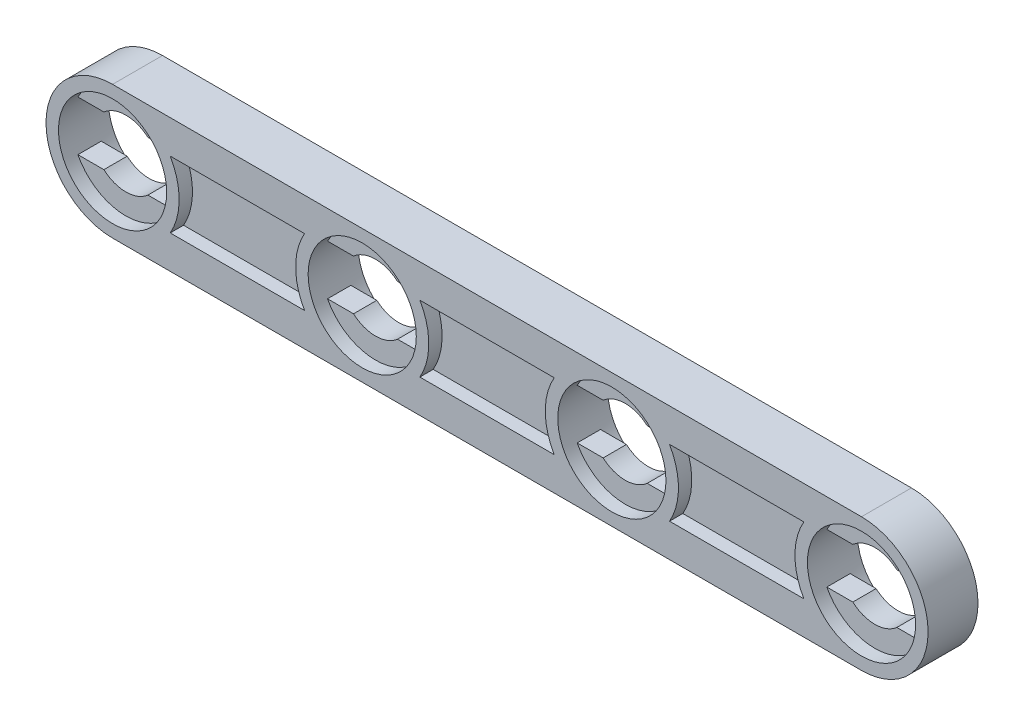
SolidWorks part; units mm, degrees
ref_plane "前视基准面" through (0, 0, 0) normal (0, 0, 1) x (1, 0, 0)
ref_plane "上视基准面" through (0, 0, 0) normal (0, 1, 0) x (1, 0, 0)
ref_plane "右视基准面" through (0, 0, 0) normal (1, 0, 0) x (0, 0, -1)
sketch "草图1" plane through (0, 0, 0) normal (0, 0, 1) x (1, 0, 0)
  line L1 (0, 4) -> (45, 4)
  line L3 (0, -4) -> (45, -4)
  arc A0 (0, 4) -> (0, -4) centre (0, 0) ccw
  arc A1 (45, -4) -> (45, 4) centre (45, 0) ccw
extrude "凸台-拉伸1" add sketch "草图1" against normal blind 3
sketch "草图2" plane through (0, 0, 0) normal (0, 0, 1) x (1, 0, 0)
  line L0 (1.3229, -1.5) -> (2.8831, -1.5)
  line L1 (-2.8831, -1.5) -> (-1.3229, -1.5)
  line L2 (1.3229, 1.5) -> (2.8831, 1.5)
  line L3 (-2.8831, 1.5) -> (-1.3229, 1.5)
  arc A0 (1.3229, 1.5) -> (-1.3229, 1.5) centre (0, 0) ccw
  arc A1 (-2.8831, 1.5) -> (-2.8831, -1.5) centre (0, 0) ccw
  arc A3 (2.8831, -1.5) -> (2.8831, 1.5) centre (0, 0) ccw
  arc A4 (-1.3229, -1.5) -> (1.3229, -1.5) centre (0, 0) ccw
extrude "切除-拉伸1" cut sketch "草图2" against normal up to next
sketch "草图3" plane through (0, 0, 0) normal (0, 0, 1) x (1, 0, 0)
  circle A1 centre (0, 0) radius 3.25
extrude "切除-拉伸2" cut sketch "草图3" against normal blind 0.8
extrude "切除-拉伸3" cut sketch "草图3<2>" along normal blind 0.8 from offset 3 offset against normal yes
sketch "草图3<2>" plane through (0, 0, 0) normal (0, 0, 1) x (1, 0, 0) same geometry as "草图3"
sketch "草图4" plane through (0, 0, 0) normal (0, 0, 1) x (1, 0, 0)
  line L1 (3.4641, 2) -> (11.5359, 2)
  line L3 (3.4641, -2) -> (11.5359, -2)
  arc A0 (11.5359, 2) -> (11.5359, -2) centre (15, 0) ccw
  arc A2 (3.4641, -2) -> (3.4641, 2) centre (0, 0) ccw
extrude "切除-拉伸4" cut sketch "草图4" against normal blind 0.8
sketch "草图5" plane through (0, 0, -3) normal (0, 0, -1) x (-1, 0, 0)
  line L1 (-4, -2) -> (-11, -2)
  line L2 (-4, -2) -> (-4, 2)
  line L3 (-4, 2) -> (-11, 2)
  line L4 (-11, -2) -> (-11, 2)
extrude "切除-拉伸6" cut sketch "草图5" against normal blind 0.8
ref_plane "基准面1" through (7.5, 0, 0) normal (1, 0, 0) x (0, 0, -1)
mirror "镜向1" about plane through (7.5, 0, 0) normal (1, 0, 0) of "切除-拉伸3", "切除-拉伸2", "切除-拉伸1"
ref_plane "基准面2" through (22.5, 0, 0) normal (1, 0, 0) x (0, 0, -1)
mirror "镜向2" about plane through (22.5, 0, 0) normal (1, 0, 0) of "镜向1", "切除-拉伸3", "切除-拉伸2", "切除-拉伸1"
ref_plane "基准面3" through (15, 0, 0) normal (1, 0, 0) x (0, 0, -1)
mirror "镜向3" about plane through (15, 0, 0) normal (1, 0, 0) of "切除-拉伸6", "切除-拉伸4"
mirror "镜向4" about plane through (22.5, 0, 0) normal (1, 0, 0) of "切除-拉伸4", "切除-拉伸6"
